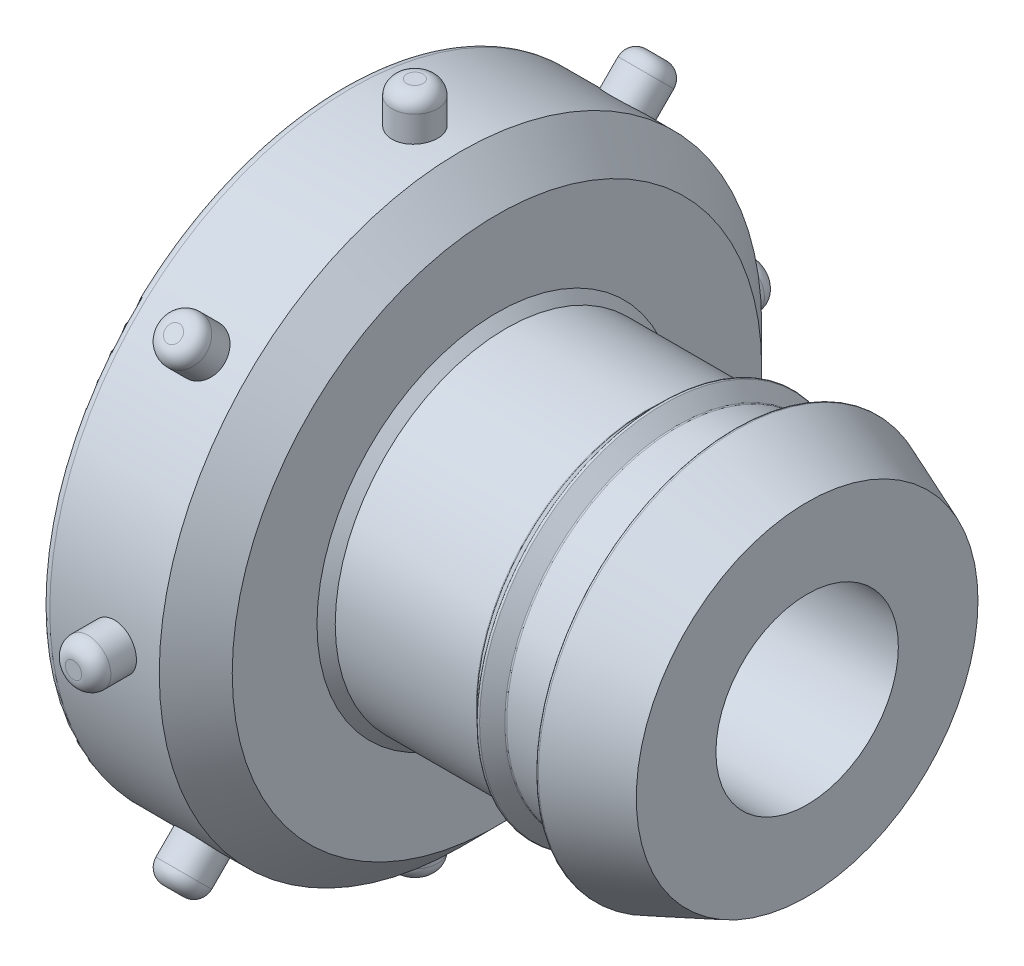
SolidWorks part; units mm, degrees
ref_plane "Front Plane" through (0, 0, 0) normal (0, 0, 1) x (1, 0, 0)
ref_plane "Top Plane" through (0, 0, 0) normal (0, 1, 0) x (1, 0, 0)
ref_plane "Right Plane" through (0, 0, 0) normal (1, 0, 0) x (0, 0, -1)
sketch "Sketch1" plane through (0, 0, 0) normal (0, 1, 0) x (1, 0, 0)
  line L0 (0, 0) -> (-17, 0)
  line L1 (0, 0) -> (0, 9.365)
  line L2 (0, 9.365) -> (-3.97, 10.955)
  line L3 (-3.97, 10.955) -> (-3.97, 9.365)
  line L4 (0, 9.365) -> (-19.3321, 9.365) construction
  line L5 (-3.97, 9.365) -> (-7.15, 9.365)
  line L6 (-7.15, 9.365) -> (-7.94, 10.155)
  line L7 (-7.94, 10.155) -> (-8.73, 9.365)
  line L8 (-8.73, 9.365) -> (-17, 9.365)
  line L9 (-17, 9.365) -> (-17, 0)
  dimension "D1" = 17
  dimension "D2" = 9.365
  dimension "D3" = 1.59
  dimension "D4" = 3.97
  dimension "D5" = 7.94
  dimension "D6" = 0.79
revolve "Revolve1" add sketch "Sketch1" angle 360 about L0
sketch "Sketch2" plane through (-17, 0, 0) normal (-1, 0, 0) x (0, 0, 1)
  circle A0 centre (0, 0) radius 9.365
  circle A1 centre (0, 0) radius 9.365 construction
  circle A2 centre (0, 0) radius 5
  circle A3 centre (0, 0) radius 16.51
  circle M3 centre (0, 0) radius 9.365
  dimension "D1" = 10
  dimension "D2" = 33.02
extrude "Boss-Extrude1" add sketch "Sketch2" along normal blind 8.5 contours A3 M3 | A2 M3 region at (-17, 0, -9.1001) region at (-17, 0, -16.043)
ref_axis "Axis1" through (-25.5, -18.161, 0) along (0, 1, 0)
sketch "Sketch4" plane through (-25.5, 0, 0) normal (-1, 0, 0) x (0, 0, 1)
  line L0 (0, -18.161) -> (0, 18.161) construction
  line L1 (9.09, 6.63) -> (-9.09, 6.63)
  line L2 (9.09, 6.63) -> (9.09, -6.92)
  line L3 (9.09, -6.92) -> (-9.09, -6.92)
  line L4 (-9.09, 6.63) -> (-9.09, -6.92)
  circle A1 centre (0, 0) radius 16.51 construction
  point P6 (0, 6.63)
  dimension "D1" = 18.18
  dimension "D2" = 13.55
  dimension "D3" = 6.92
extrude "Cut-Extrude1" cut sketch "Sketch4" against normal blind 7
sketch "Sketch5" plane through (-25.5, 0, 0) normal (-1, 0, 0) x (0, 0, 1)
  circle A0 centre (0, 0) radius 14.14
  dimension "D1" = 28.28
sketch "Sketch6" plane through (0, 0, 0) normal (0, 0, 1) x (1, 0, 0)
  line L0 (-25.5, 14.14) -> (-25.5, -14.14) construction
  circle A0 centre (-25.5, 14.14) radius 0.9
  point P0 (-25.5, 14.14)
  dimension "D1" = 1.8
ref_axis "Axis2" through (-35.0271, 0, 0) along (1, 0, 0)
revolve "Cut-Revolve1" cut sketch "Sketch6" angle 360 about axis through (-35.0271, 0, 0) along (1, 0, 0)
fillet "Fillet1" radius 1 1 edges at (-25.5, 0, -13.24)
ref_plane "Plane1" through (-21.5, 0, 0) normal (-1, 0, 0) x (0, 0, 1)
ref_axis "Axis3" through (-21.5, -18.161, 0) along (0, 1, 0)
ref_plane "Plane2" through (0, 16.51, 0) normal (0, 1, 0) x (1, 0, 0)
sketch "Sketch7" plane through (0, 16.51, 0) normal (0, 1, 0) x (1, 0, 0)
  circle A0 centre (-21.5, 0) radius 1.25
  dimension "D1" = 2.5
extrude "Boss-Extrude2" add sketch "Sketch7" along normal blind 2.2 and the other way blind 2 contours A0
fillet "Fillet2" radius 0.8 1 edges at (-21.5, 18.71, 1.25)
pattern_circular "CirPattern1" count 8 over 360 about axis through (-25.5, 0, 0) along (1, 0, 0) of "Boss-Extrude2", "Fillet2"
chamfer "Chamfer1" distance 2 angle 45 1 edges at (-17, 0, 16.51)
fillet "Fillet3" radius 0.5 1 edges at (-25.5, 0, 16.51)
fillet "Fillet4" radius 0.1 5 edges at (-8.73, 0, -9.365) (-7.94, 0, -10.155) (-7.15, 0, -9.365) (-3.97, 0, -9.365) (-3.97, 0, -10.955)
chamfer "Chamfer2" distance 0.5 angle 45 1 edges at (-17, 0, 9.365)
extrude "Cut-Extrude2" cut sketch "Sketch2<3>" against normal through all both and the other way through all contours A2 region at (-17, 0, 0)
sketch "Sketch2<3>" plane through (-17, 0, 0) normal (-1, 0, 0) x (0, 0, 1) same geometry as "Sketch2"
chamfer "Chamfer3" distance 1 angle 76 1 edges at (-25.5, -6.92, 0) first distance on face at (-25.5, 0, 12.5245)
sketch "Sketch8" plane through (-18.5, 0, 0) normal (-1, 0, 0) x (0, 0, 1)
  line L1 (-9.09, -6.92) -> (-5, -6.92)
  line L2 (-9.09, -6.92) -> (-9.09, 0.73)
  line L3 (-9.09, 0.73) -> (-5, 0.73)
  line L4 (-5, -6.92) -> (-5, 0.73)
  circle A0 centre (0, 0) radius 5 construction
  dimension "D1" = 7.65
extrude "Boss-Extrude3" add sketch "Sketch8" along normal blind 0.64
fillet "Fillet5" radius 0.5 2 edges at (-19.14, 0.73, -7.045) (-19.14, -3.095, -5)
chamfer "Chamfer4" distance 3 angle 45 1 edges at (-18.5, 0, -5)
equation "\"WallThick\"= 1.2'thickness of wall for printer"
equation "\"dHole\"= 3.3'diameter of screw hole"
equation "\"D3@Sketch4\"=33.02/2-9.59"
equation "\"D1@Boss-Extrude2\"=(37.42-33.02)/2"
